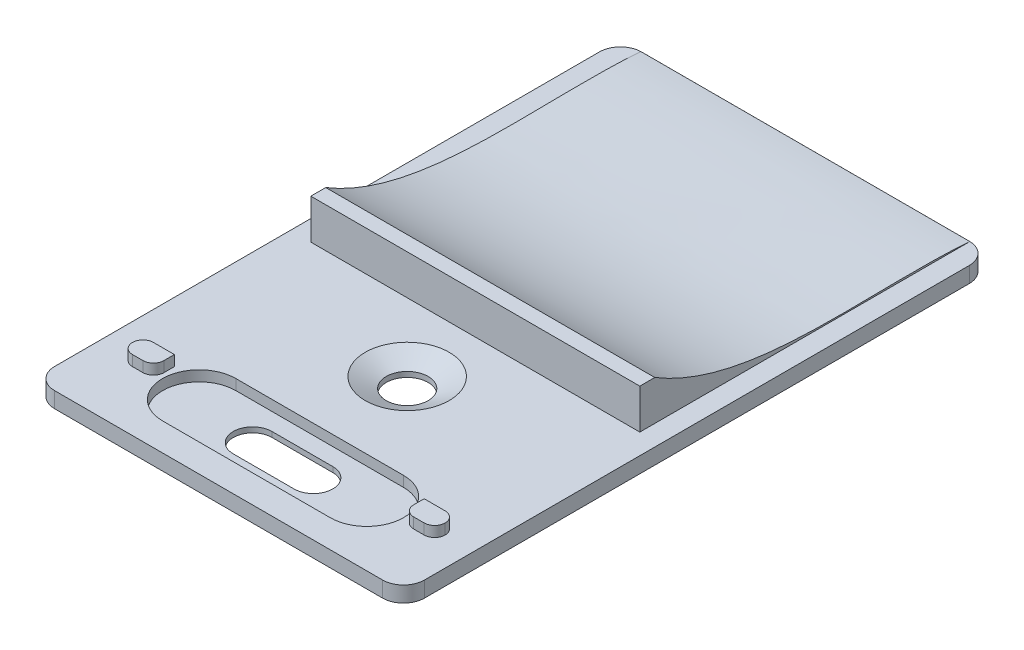
SolidWorks part; units mm, degrees
ref_plane "Front Plane" through (0, 0, 0) normal (0, 0, 1) x (1, 0, 0)
ref_plane "Top Plane" through (0, 0, 0) normal (0, 1, 0) x (1, 0, 0)
ref_plane "Right Plane" through (0, 0, 0) normal (1, 0, 0) x (0, 0, -1)
sketch "Sketch1" plane through (0, 0, 0) normal (0, 1, 0) x (1, 0, 0)
  line L1 (-17.65, 13) -> (17.65, 13)
  line L2 (-17.65, 13) -> (-17.65, -13)
  line L3 (-17.65, -13) -> (17.65, -13)
  line L4 (17.65, 13) -> (17.65, -13)
  line L5 (-17.65, 13) -> (17.65, -13) construction
  line L6 (-17.65, -13) -> (17.65, 13) construction
  point P0 (0, 0)
  dimension "D1" = 35.3
  dimension "D2" = 26
extrude "Boss-Extrude1" add sketch "Sketch1" along normal blind 1.5
sketch "Sketch2" plane through (0, 1.5, 0) normal (0, 1, 0) x (1, 0, 0)
  line L0 (17.65, 13) -> (-17.65, 13) construction
  line L1 (-15.9, 13) -> (15.9, 13)
  line L2 (-15.9, 13) -> (-15.9, 11.5)
  line L3 (-15.9, 11.5) -> (15.9, 11.5)
  line L4 (15.9, 13) -> (15.9, 11.5)
  point P6 (0, 11.5)
  dimension "D1" = 0
  dimension "D2" = 31.8
  dimension "D3" = 1.5
extrude "Boss-Extrude2" add sketch "Sketch2" along normal blind 3.8
sketch "Sketch3" plane through (0, 1.5, 0) normal (0, 1, 0) x (1, 0, 0)
  line L0 (-17.65, -13) -> (17.65, -13) construction
  circle A0 centre (0, 5) radius 2
  dimension "D1" = 18
  dimension "D2" = 4
extrude "Cut-Extrude1" cut sketch "Sketch3" against normal through all both and the other way through all
chamfer "Chamfer1" distance 2 distance2 1 1 edges at (0, 1.5, -3) first distance on face at (0, 1.5, -3)
fillet "Fillet1" radius 2 2 edges at (-17.65, 0.75, 13) (17.65, 0.75, 13)
sketch "Sketch4" plane through (0, 0, -13) normal (0, 0, -1) x (-1, 0, 0)
  line L0 (-15.9, 5.3) -> (-15.9, 1.5)
  line L1 (-15.9, 1.5) -> (-17.65, 1.5)
  line L2 (-17.65, 1.5) -> (-17.65, 0)
  line L3 (19.5981, 0) -> (-19.5981, 0) construction
  line L4 (-17.65, 1.5) -> (-17.65, 0) construction
  line L5 (-17.65, 0) -> (17.65, 0)
  line L6 (-17.65, 0) -> (17.65, 0) construction
  line L7 (17.65, 0) -> (17.65, 1.5)
  line L8 (17.65, 1.5) -> (15.9, 1.5)
  line L9 (15.9, 1.5) -> (15.9, 5.3)
  line L10 (15.9, 5.3) -> (-15.9, 5.3)
extrude "Boss-Extrude3" add sketch "Sketch4" along normal blind 30
fillet "Fillet2" radius 2 2 edges at (-17.65, 0.75, -43) (17.65, 0.75, -43)
fillet "Fillet3" [suppressed] radius 20
sketch "Sketch6" plane through (0, 1.5, 0) normal (0, 1, 0) x (1, 0, 0)
  line L7 (-17.65, 41) -> (-17.65, -11) construction
  line L8 (-14.92, -7.3) -> (-11.92, -7.3)
  line L9 (-14.92, -7.3) -> (-14.92, -5.3)
  line L10 (-14.92, -5.3) -> (-11.92, -5.3)
  line L11 (-11.92, -7.3) -> (-11.92, -5.3)
  line L12 (-15.65, -13) -> (15.65, -13) construction
  line L13 (0, -13) -> (0, -7.6395) construction
  line L14 (14.92, -5.3) -> (11.92, -5.3)
  line L15 (11.92, -7.3) -> (11.92, -5.3)
  line L16 (14.92, -7.3) -> (11.92, -7.3)
  line L17 (14.92, -7.3) -> (14.92, -5.3)
  dimension "D1" = 2.73
  dimension "D2" = 5.7
  dimension "D3" = 3
  dimension "D4" = 2
extrude "Boss-Extrude4" add sketch "Sketch6" along normal blind 1
fillet "Fillet4" radius 1 6 edges at (-14.92, 2, 5.3) (14.92, 2, 5.3) (14.92, 2, 7.3) (11.92, 2, 7.3) (-11.92, 2, 7.3) (-14.92, 2, 7.3)
sketch "Sketch7" plane through (0, 0, -11.5) normal (0, 0, 1) x (1, 0, 0)
  line L0 (-15.9, 1.5) -> (15.9, 1.5) construction
  line L1 (-15.7, 1.5) -> (-17.444, 1.5)
  line L2 (-15.7, 1.5) -> (-15.7, 7.8507)
  line L3 (-15.7, 7.8507) -> (-17.444, 7.8507)
  line L4 (-17.444, 1.5) -> (-17.444, 7.8507)
  line L5 (-15.9, 5.3) -> (-15.9, 1.5) construction
  line L6 (15.9, 5.3) -> (15.9, 1.5) construction
  line L7 (15.7, 1.5) -> (17.983, 1.5)
  line L8 (15.7, 1.5) -> (15.7, 9.1492)
  line L9 (15.7, 9.1492) -> (17.983, 9.1492)
  line L10 (17.983, 1.5) -> (17.983, 9.1492)
  dimension "D1" = 0.2
  dimension "D2" = 0.2
extrude "Cut-Extrude2" cut sketch "Sketch7" against normal through all
sketch "Sketch8" plane through (0, 1.5, 0) normal (0, 1, 0) x (1, 0, 0)
  line L0 (-7.5, -2.5) -> (7.5, -2.5) construction
  line L1 (-7.5, -0.9153) -> (7.5, -0.9153)
  line L2 (-7.5, -4.0847) -> (7.5, -4.0847)
  line L3 (-15.65, -13) -> (15.65, -13) construction
  arc A0 (-7.5, -0.9153) -> (-7.5, -4.0847) centre (-7.5, -2.5) ccw
  arc A1 (7.5, -4.0847) -> (7.5, -0.9153) centre (7.5, -2.5) ccw
  point P2 (0, -2.5)
  point P9 (0, -13)
  dimension "D1" = 0
  dimension "D2" = 10.5
  dimension "D3" = 15
extrude "Cut-Extrude3" [suppressed] cut sketch "Sketch8" against normal through all
sketch "Sketch9" [suppressed] plane through (0, 0, 0) normal (0, -1, 0) x (1, 0, 0)
  line L0 (-6.5847, 2.5) -> (6.5847, 2.5) construction
  line L1 (-6.5847, 6.5) -> (6.5847, 6.5)
  line L2 (-6.5847, -1.5) -> (6.5847, -1.5)
  arc A0 (-6.5847, 6.5) -> (-6.5847, -1.5) centre (-6.5847, 2.5) ccw
  arc A1 (6.5847, -1.5) -> (6.5847, 6.5) centre (6.5847, 2.5) ccw
  arc A2 (-7.5, 4.0847) -> (-7.5, 0.9153) centre (-7.5, 2.5) ccw construction
  arc A3 (7.5, 0.9153) -> (7.5, 4.0847) centre (7.5, 2.5) ccw construction
  point P2 (0, 2.5)
  point P7 (-10.5847, 2.5)
  point P11 (-9.0847, 2.5)
  point P12 (10.5847, 2.5)
  point P16 (9.0847, 2.5)
  dimension "D1" = 8
  dimension "D2" = 1.5
  dimension "D3" = 1.5
  dimension "D4" = 0
extrude "Cut-Extrude4" [suppressed] cut sketch "Sketch9" along normal offset from surface (0.8 mm away) 0.7 from surface up to face at (0, 0, -3) starting at face at (0, 1.5, -14.2964)
sketch "Sketch10" plane through (15.7, 0, 0) normal (1, 0, 0) x (0, 0, -1)
  line L0 (42.9994, 5.3) -> (11.5, 5.3) construction
  line L2 (12.9252, 5.3) -> (13.3546, 9.3095)
  line L3 (13.3546, 9.3095) -> (48.3787, 9.9202)
  line L4 (48.3787, 9.9202) -> (42.9994, 1.5)
  spline S0 degree 3 poles (12.9252, 5.3) (21.8838, -0.1168) (33.3186, 2.2835) (42.9994, 1.5) knots 0 0 0 0 1 1 1 1
  point P2 (48.3787, 9.9202)
extrude "Cut-Extrude5" cut sketch "Sketch10" against normal through all both and the other way through all
sketch "Sketch12" plane through (0, 1.5, 0) normal (0, 1, 0) x (1, 0, 0)
  line L0 (-2.9, -6.85) -> (2.9, -6.85) construction
  line L1 (-2.9, -5) -> (2.9, -5)
  line L2 (-2.9, -8.7) -> (2.9, -8.7)
  line L3 (-15.65, -13) -> (15.65, -13) construction
  arc A0 (-2.9, -5) -> (-2.9, -8.7) centre (-2.9, -6.85) ccw
  arc A1 (2.9, -8.7) -> (2.9, -5) centre (2.9, -6.85) ccw
  point P2 (0, -6.85)
  point P9 (0, -13)
  point P10 (4.75, -6.85)
  point P11 (-4.75, -6.85)
  dimension "D1" = 4.3
  dimension "D2" = 8
  dimension "D3" = 0
  dimension "D4" = 9.5
extrude "Cut-Extrude6" cut sketch "Sketch12" against normal through all both
sketch "Sketch13" plane through (0, 0, 0) normal (0, -1, 0) x (1, 0, 0)
  line L0 (-8, 6.85) -> (8, 6.85) construction
  line L1 (-8, 10.35) -> (8, 10.35)
  line L2 (-8, 3.35) -> (8, 3.35)
  line L3 (2.9, 5) -> (-2.9, 5) construction
  arc A0 (-8, 10.35) -> (-8, 3.35) centre (-8, 6.85) ccw
  arc A1 (8, 3.35) -> (8, 10.35) centre (8, 6.85) ccw
  arc A2 (-2.9, 8.7) -> (-2.9, 5) centre (-2.9, 6.85) ccw construction
  point P2 (0, 6.85)
  point P7 (-11.5, 6.85)
  point P8 (11.5, 6.85)
  point P12 (-4.75, 6.85)
  point P15 (0, 5)
  dimension "D1" = 7
  dimension "D2" = 23
  dimension "D3" = 0
  dimension "D4" = 0
extrude "Cut-Extrude7" cut sketch "Sketch13" along normal offset from surface (1 mm away) 0.5 from surface up to face at (0, 0, 6.85) starting at face at (0, 1.5, 6.85)
